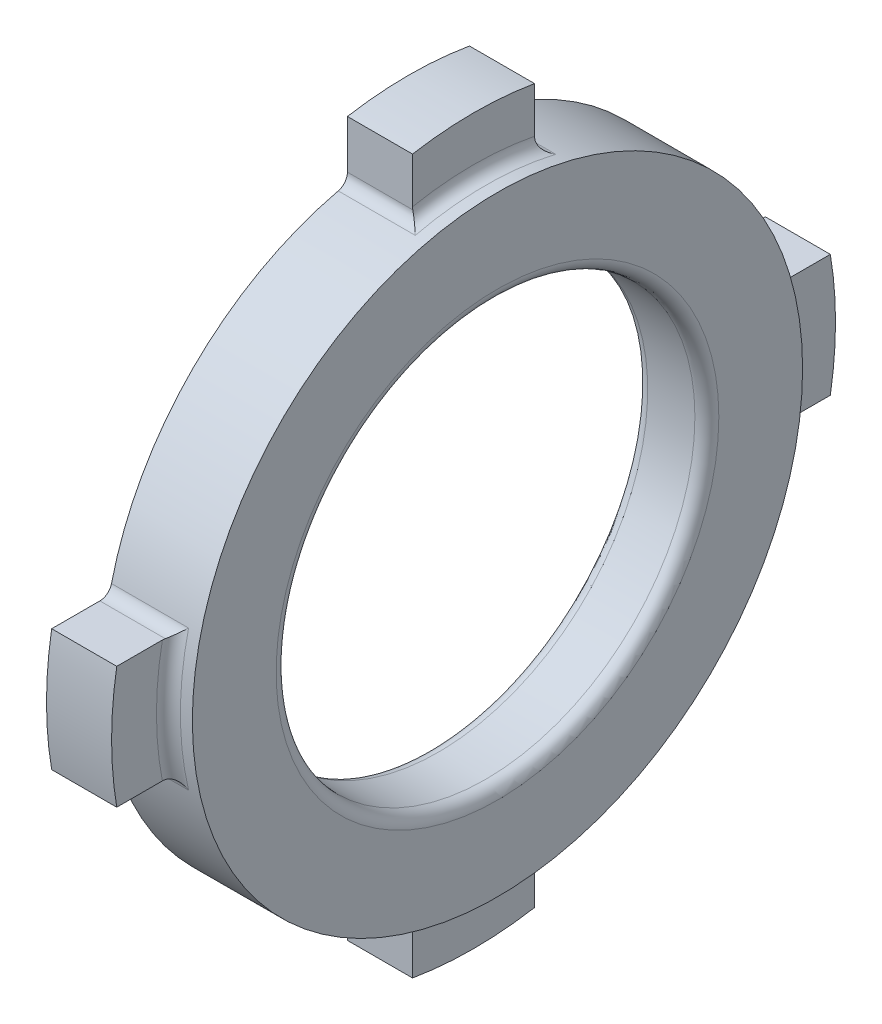
SolidWorks part; units mm, degrees
material "Plain Carbon Steel"
ref_plane "Front Plane" through (0, 0, 0) normal (0, 0, 1) x (1, 0, 0)
ref_plane "Top Plane" through (0, 0, 0) normal (0, 1, 0) x (1, 0, 0)
ref_plane "Right Plane" through (0, 0, 0) normal (1, 0, 0) x (0, 0, -1)
sketch "Sketch1" plane through (0, 0, 0) normal (1, 0, 0) x (0, 0, -1)
  line L0 (-5.1, 29.817) -> (-5.1, 24.9848)
  line L1 (5.1, 29.817) -> (5.1, 24.9848)
  line L2 (29.817, 5.1) -> (24.9848, 5.1)
  line L3 (29.817, -5.1) -> (24.9848, -5.1)
  line L4 (5.1, -29.817) -> (5.1, -24.9848)
  line L5 (-5.1, -29.817) -> (-5.1, -24.9848)
  line L6 (-29.817, -5.1) -> (-24.9848, -5.1)
  line L7 (-29.817, 5.1) -> (-24.9848, 5.1)
  circle A0 centre (0, 0) radius 17.5
  circle A1 centre (0, 0) radius 25.5
  circle A2 centre (0, 0) radius 30.25
  dimension "D1" = 35
  dimension "D2" = 51
  dimension "D3" = 60.5
  dimension "D4" = 10.2
  dimension "D5" = 5.1
extrude "Extrude1" add sketch "Sketch1" along normal blind 7.44 contours A1 A0 | L7 A2 L6 A1 | L5 A2 L4 A1 | L3 A2 L2 A1 | L1 A2 L0 A1 region at (0, 27.7168, 0) region at (0, 24.7788, 0) region at (0, 0, 27.7168) region at (0, 0, -27.7168) region at (0, -27.7168, 0)
sketch "Sketch2" plane through (7.44, 0, 0) normal (1, 0, 0) x (0, 0, -1)
  circle A0 centre (0, 0) radius 25.5
  circle A1 centre (0, 0) radius 30.25
extrude "Extrude2" cut sketch "Sketch2" against normal blind 2
sketch "Sketch3" plane through (0, 0, 0) normal (-1, 0, 0) x (0, 0, 1)
  circle A0 centre (0, 0) radius 17.5
  circle A1 centre (0, 0) radius 22
  arc A2 (-5.1, 24.9848) -> (-24.9848, 5.1) centre (0, 0) ccw construction
  dimension "D1" = 3.5
extrude "Extrude3" cut sketch "Sketch3" against normal blind 1.5
fillet "Fillet1" radius 1 14 edges at (1.5, 0, 17.5) (7.44, 0, -17.5) (5.44, 0, -25.5) (5.44, -25.5, 0) (5.44, 0, 25.5) (5.44, 25.5, 0) (2.72, 5.1, -24.9848) (2.72, -5.1, -24.9848) (2.72, -24.9848, -5.1) (2.72, -24.9848, 5.1) (2.72, -5.1, 24.9848) (2.72, 5.1, 24.9848) (2.72, 24.9848, -5.1) (2.72, 24.9848, 5.1)
